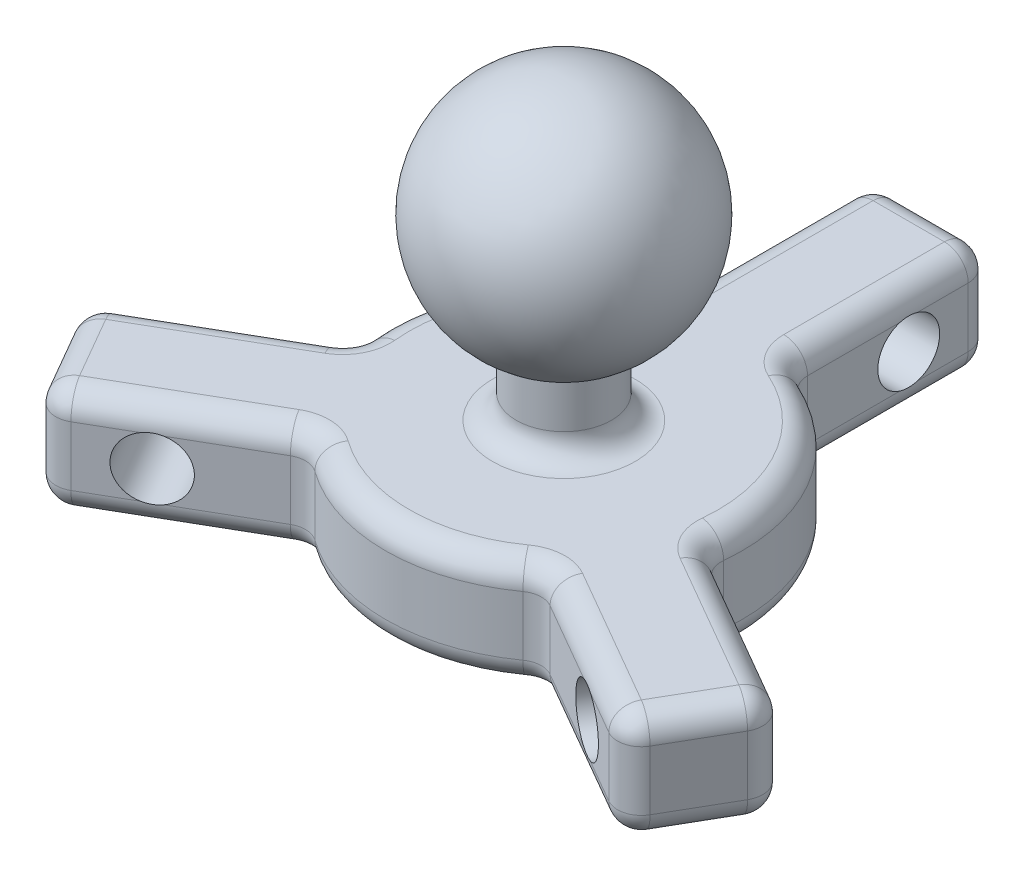
SolidWorks part; units mm, degrees
ref_plane "Front Plane" through (0, 0, 0) normal (0, 0, 1) x (1, 0, 0)
ref_plane "Top Plane" through (0, 0, 0) normal (0, 1, 0) x (1, 0, 0)
ref_plane "Right Plane" through (0, 0, 0) normal (1, 0, 0) x (0, 0, -1)
sketch "Sketch1" plane through (0, 0, 0) normal (0, 1, 0) x (1, 0, 0)
  line L0 (0, 0) -> (0, 36.5368) construction
  line L1 (0, 24) -> (-36.4215, 24) construction
  line L2 (-5, 31) -> (-5, 14.1421)
  line L3 (-5, 31) -> (5, 31)
  line L4 (5, 31) -> (5, 14.1421)
  line L5 (29.3468, -11.1699) -> (14.7474, -2.7409)
  line L6 (29.3468, -11.1699) -> (24.3468, -19.8301)
  line L7 (24.3468, -19.8301) -> (9.7474, -11.4012)
  line L8 (-24.3468, -19.8301) -> (-9.7474, -11.4012)
  line L9 (-24.3468, -19.8301) -> (-29.3468, -11.1699)
  line L10 (-29.3468, -11.1699) -> (-14.7474, -2.7409)
  circle A0 centre (0, 0) radius 24 construction
  arc A1 (-5, 14.1421) -> (-14.7474, -2.7409) centre (0, 0) ccw
  arc A2 (-9.7474, -11.4012) -> (9.7474, -11.4012) centre (0, 0) ccw
  arc A3 (14.7474, -2.7409) -> (5, 14.1421) centre (0, 0) ccw
  point P12 (0, 31)
  point P21 (0, 0)
  dimension "D1" = 48
  dimension "D2" = 30
  dimension "D3" = 5
  dimension "D4" = 7
  dimension "D5" = 3
extrude "Boss-Extrude1" add sketch "Sketch1" along normal blind 9
sketch "Sketch2" plane through (2.5, 0, 4.3301) normal (0.5, 0, 0.866) x (0.866, 0, -0.5)
  line L0 (-31, 4.5) -> (-14.1421, 4.5) construction
  line L1 (-31, 9) -> (-31, 0) construction
  line L2 (-14.1421, 9) -> (-14.1421, 0) construction
  circle A0 centre (-24, 4.5) radius 2.6
  dimension "D1" = 5.2
  dimension "D2" = 24
extrude "Cut-Extrude1" cut sketch "Sketch2" against normal through all
pattern_circular "CirPattern1" count 3 every 120 about axis through (0, 9, 0) along (0, 1, 0) of "Cut-Extrude1"
sketch "Sketch3" plane through (0, 9, 0) normal (0, 1, 0) x (1, 0, 0)
  circle A0 centre (0, 0) radius 4
  dimension "D1" = 8
extrude "Boss-Extrude2" add sketch "Sketch3" along normal blind 15 contours A0
sketch "Sketch4" plane through (0, 24, 0) normal (0, 1, 0) x (1, 0, 0)
  line L0 (0, 10) -> (0, -10)
  arc A0 (0, -10) -> (0, 10) centre (0, 0) ccw
  dimension "D1" = 20
revolve "Revolve1" add sketch "Sketch4" angle 360 about L0 region at (4.7292, 24, 0)
fillet "Fillet1" radius 2 37 edges at (5, 4.5, -31) (-5, 4.5, -31) (-5, 4.5, -14.1421) (-14.7474, 4.5, 2.7409) (14.7474, 4.5, 2.7409) (5, 4.5, -14.1421) (24.3468, 4.5, 19.8301) (29.3468, 4.5, 11.1699) (-29.3468, 4.5, 11.1699) (-24.3468, 4.5, 19.8301) (-9.7474, 4.5, 11.4012) (9.7474, 4.5, 11.4012) (22.0471, 0, 6.9554) (12.9904, 0, -7.5) (5, 0, -22.5711) (0, 0, -31) (-5, 0, -22.5711) (-12.9904, 0, -7.5) (-22.0471, 0, 6.9554) (-26.8468, 0, 15.5) (-17.0471, 0, 15.6157) (0, 0, 15) (17.0471, 0, 15.6157) (26.8468, 0, 15.5) (17.0471, 9, 15.6157) (0, 9, 15) (-17.0471, 9, 15.6157) (-26.8468, 9, 15.5) (-22.0471, 9, 6.9554) (-12.9904, 9, -7.5) (-5, 9, -22.5711) (0, 9, -31) (5, 9, -22.5711) (12.9904, 9, -7.5) (22.0471, 9, 6.9554) (26.8468, 9, 15.5) (0, 9, 4)
